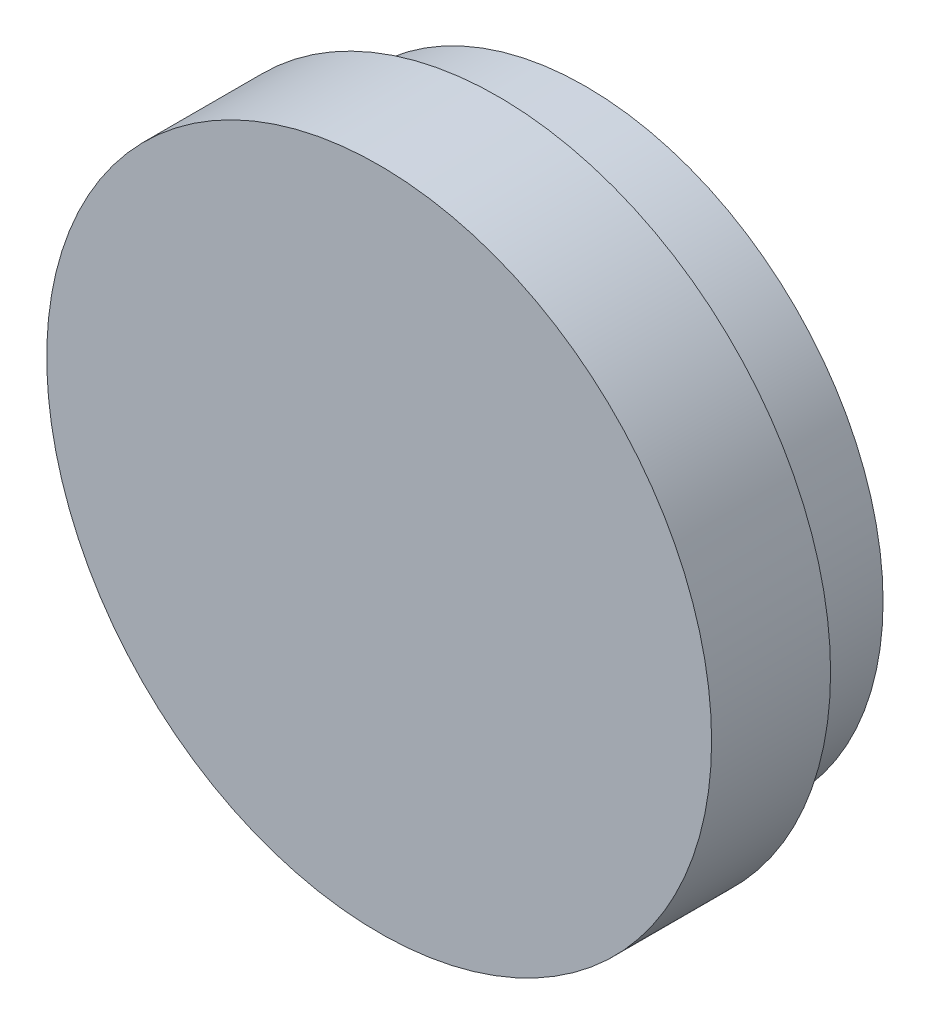
SolidWorks part; units mm, degrees
material "ABS"
ref_plane "正面" through (0, 0, 0) normal (0, 0, 1) x (1, 0, 0)
ref_plane "平面" through (0, 0, 0) normal (0, 1, 0) x (1, 0, 0)
ref_plane "右側面" through (0, 0, 0) normal (1, 0, 0) x (0, 0, -1)
sketch "ｽｹｯﾁ1" plane through (0, 0, 0) normal (0, 0, 1) x (1, 0, 0)
  circle A0 centre (0, 0) radius 8.5
  dimension "D1" = 17
extrude "ﾎﾞｽ - 押し出し1" add sketch "ｽｹｯﾁ1" along normal blind 2.5
sketch "ｽｹｯﾁ2" plane through (0, 0, 2.5) normal (0, 0, 1) x (1, 0, 0)
  circle A0 centre (0, 0) radius 9.5
  dimension "D1" = 19
extrude "ﾎﾞｽ - 押し出し2" add sketch "ｽｹｯﾁ2" along normal blind 3.4
